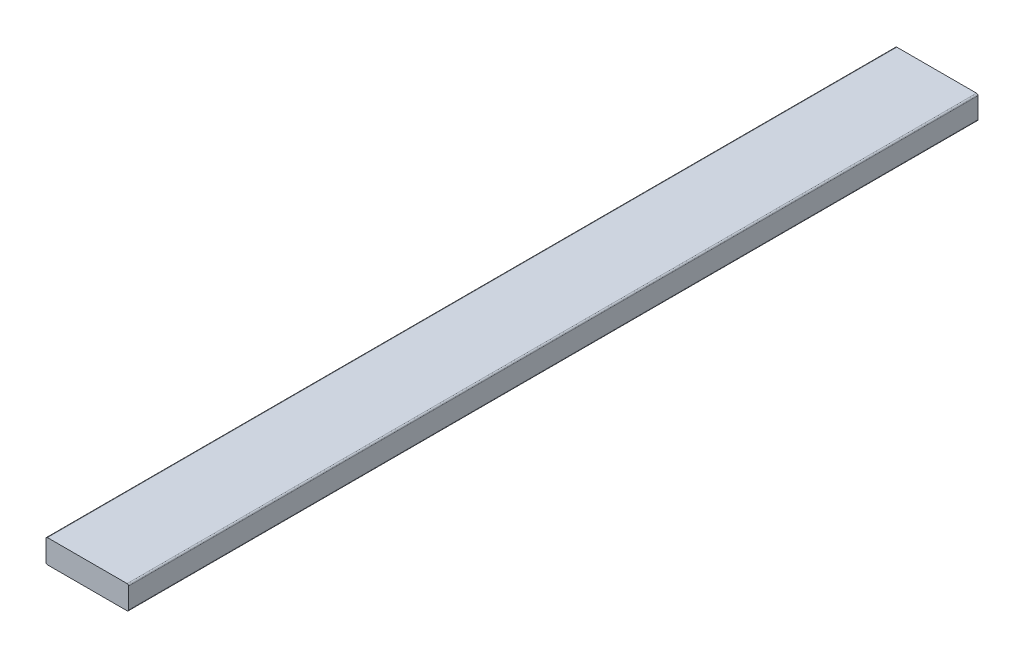
SolidWorks part; units mm, degrees
material "Cedar"
ref_plane "Front Plane" through (0, 0, 0) normal (0, 0, 1) x (1, 0, 0)
ref_plane "Top Plane" through (0, 0, 0) normal (0, 1, 0) x (1, 0, 0)
ref_plane "Right Plane" through (0, 0, 0) normal (1, 0, 0) x (0, 0, -1)
sketch "Sketch1" plane through (0, 0, 0) normal (0, 0, 1) x (1, 0, 0)
  line L1 (-44.45, -12.7) -> (44.45, -12.7)
  line L2 (-44.45, -12.7) -> (-44.45, 12.7)
  line L3 (-44.45, 12.7) -> (44.45, 12.7)
  line L4 (44.45, -12.7) -> (44.45, 12.7)
  line L5 (-44.45, -12.7) -> (44.45, 12.7) construction
  line L6 (-44.45, 12.7) -> (44.45, -12.7) construction
  point P0 (0, 0)
  dimension "D1" = 88.9
  dimension "D2" = 25.4
extrude "Boss-Extrude1" add sketch "Sketch1" along normal blind 914.4
fillet "Fillet1" radius 1.5875 4 edges at (-44.45, -12.7, 457.2) (44.45, -12.7, 457.2) (-44.45, 12.7, 457.2) (44.45, 12.7, 457.2)
